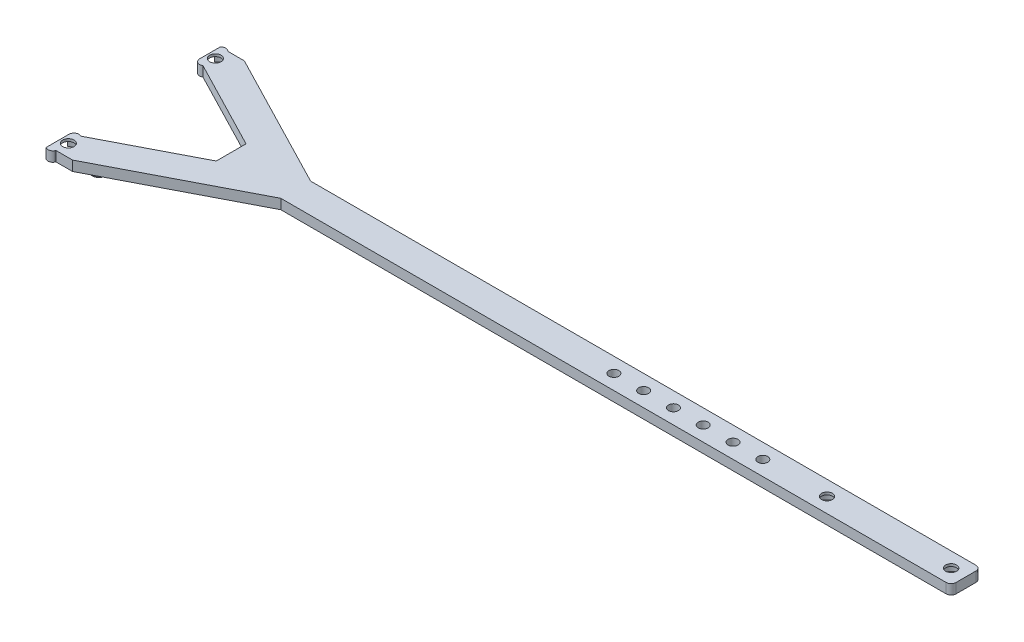
SolidWorks part; units mm, degrees
ref_plane "Płaszczyzna przednia" through (0, 0, 0) normal (0, 0, 1) x (1, 0, 0)
ref_plane "Płaszczyzna górna" through (0, 0, 0) normal (0, 1, 0) x (1, 0, 0)
ref_plane "Płaszczyzna prawa" through (0, 0, 0) normal (1, 0, 0) x (0, 0, -1)
sketch "Szkic1" plane through (0, -0.6011, 0) normal (0, -1, 0) x (1, 0, 0)
  line L0 (-40.95, 47.1335) -> (-28.6, 47.1335) construction
  line L1 (-28.6, 41.1335) -> (-40.95, 41.1335) construction
  line L2 (-159.9499, 47.1335) -> (-28.6, 47.1335)
  line L3 (-28.6, 41.1335) -> (-159.9499, 41.1335)
  line L4 (-28.6, 41.1335) -> (-11.9498, 41.1335)
  line L5 (-11.9498, 41.1335) -> (-11.9498, 47.1335)
  line L6 (-11.9498, 47.1335) -> (-28.6, 47.1335)
  line L7 (-159.9499, 41.1335) -> (-159.9499, 47.1335)
  circle A0 centre (-14.9498, 44.1337) radius 1.1 construction
  circle A1 centre (-39.9499, 44.1337) radius 1.1 construction
  circle A2 centre (-14.9498, 44.1337) radius 1.1
  circle A3 centre (-39.9499, 44.1337) radius 1.1
  dimension "D1" = 3
  dimension "D2" = 120
extrude "Dodanie-wyciągnięcie1" add sketch "Szkic1" along normal blind 2
sketch "Szkic2" plane through (0, -0.6011, 0) normal (0, 1, 0) x (1, 0, 0)
  line L0 (-177.9299, -26.8335) -> (-178.5249, -25.6335) construction
  line L1 (-179.4499, -32.9335) -> (-177.9299, -31.8335) construction
  line L2 (-178.5249, -62.6335) -> (-177.9299, -61.4335) construction
  line L3 (-177.9299, -56.4335) -> (-179.4499, -55.3335) construction
  line L4 (-177.9299, -26.8335) -> (-178.5249, -25.6335)
  line L5 (-179.4499, -32.9335) -> (-177.9299, -31.8335)
  line L6 (-178.5249, -62.6335) -> (-177.9299, -61.4335)
  line L7 (-177.9299, -56.4335) -> (-179.4499, -55.3335)
  line L8 (-178.5249, -25.6335) -> (-179.4499, -26.8335)
  line L9 (-179.4499, -26.8335) -> (-179.4499, -32.9335)
  line L10 (-178.5249, -62.6335) -> (-179.4499, -61.9205)
  line L11 (-179.4499, -61.9205) -> (-179.4499, -55.3335)
  line L12 (-177.9299, -26.8335) -> (-174.5965, -26.8335)
  line L13 (-174.5965, -26.8335) -> (-146.9499, -41.1335)
  line L14 (-159.9499, -41.1335) -> (-159.9499, -47.1335)
  line L15 (-159.9499, -41.1335) -> (-11.9498, -41.1335) construction
  line L16 (-174.5965, -61.4335) -> (-177.9299, -61.4335)
  line L18 (-146.9499, -47.1335) -> (-174.5965, -61.4335)
  line L19 (-11.9498, -47.1335) -> (-159.9499, -47.1335) construction
  line L20 (-177.9299, -56.4335) -> (-159.9499, -47.1335)
  line L21 (-159.9499, -41.1335) -> (-177.9299, -31.8335)
  line L22 (-146.9499, -41.1335) -> (-146.9499, -47.1335)
  circle A0 centre (-177.9297, -58.9335) radius 1.15 construction
  circle A1 centre (-177.9297, -29.3335) radius 1.15 construction
  circle A2 centre (-177.9297, -58.9335) radius 1.15
  circle A3 centre (-177.9297, -29.3335) radius 1.15
  circle A4 centre (-39.9499, -44.1337) radius 1.1 construction
  dimension "D1" = 107
extrude "Dodanie-wyciągnięcie3" add sketch "Szkic2" against normal blind 2
sketch "Szkic4" plane through (0, -2.6011, 0) normal (0, -1, 0) x (1, 0, 0)
  circle A0 centre (-14.9498, 44.1337) radius 2
  circle A1 centre (-39.9499, 44.1337) radius 2
  circle A2 centre (-177.9297, 58.9335) radius 2
  circle A3 centre (-177.9297, 29.3335) radius 2
  dimension "D1" = 4
extrude "Wytnij-wyciągnięcie2" cut sketch "Szkic4" against normal blind 1.5
sketch "Szkic6" plane through (0, -2.6011, 0) normal (0, -1, 0) x (1, 0, 0)
  line L0 (-146.9499, 41.1335) -> (-174.5965, 26.8335) construction
  line L1 (-174.5965, 61.4335) -> (-146.9499, 47.1335) construction
  line L2 (-173.3035, 59.3871) -> (-173.3035, 55.3871)
  line L3 (-173.3035, 32.8798) -> (-173.3035, 28.8798)
  arc A1 (-173.3035, 28.8798) -> (-173.3035, 32.8798) centre (-173.3035, 30.8798) ccw
  arc A2 (-173.3035, 55.3871) -> (-173.3035, 59.3871) centre (-173.3035, 57.3871) ccw
  dimension "D1" = 3
  dimension "D2" = 3
revolve "Obrót11" add sketch "Szkic6" angle 180 about L2
sketch "Szkic7" plane through (0, -0.6011, 0) normal (0, 1, 0) x (1, 0, 0)
  line L0 (-146.9499, -41.1335) -> (-11.9498, -41.1335) construction
  circle A0 centre (-52.8732, -44.1335) radius 1
  circle A1 centre (-58.8732, -44.1335) radius 1
  circle A2 centre (-64.8732, -44.1335) radius 1
  circle A3 centre (-70.8732, -44.1335) radius 1
  circle A4 centre (-76.8732, -44.1335) radius 1
  circle A5 centre (-82.8732, -44.1335) radius 1
  dimension "D2" = 2
  dimension "D1" = 3
  dimension "D3" = 6
  dimension "D4" = 6
  dimension "D5" = 6
  dimension "D6" = 6
  dimension "D7" = 6
extrude "Wytnij-wyciągnięcie3" cut sketch "Szkic7" against normal blind 3
fillet "Zaokrąglenie1" radius 1 5 edges at (-179.4499, -1.6011, 55.3335) (-178.5249, -1.6011, 62.6335) (-178.5249, -1.6011, 25.6335) (-11.9498, -1.6011, 47.1335) (-11.9498, -1.6011, 41.1335)
fillet "Zaokrąglenie2" radius 1 1 edges at (-179.4499, -1.6011, 32.9335)
